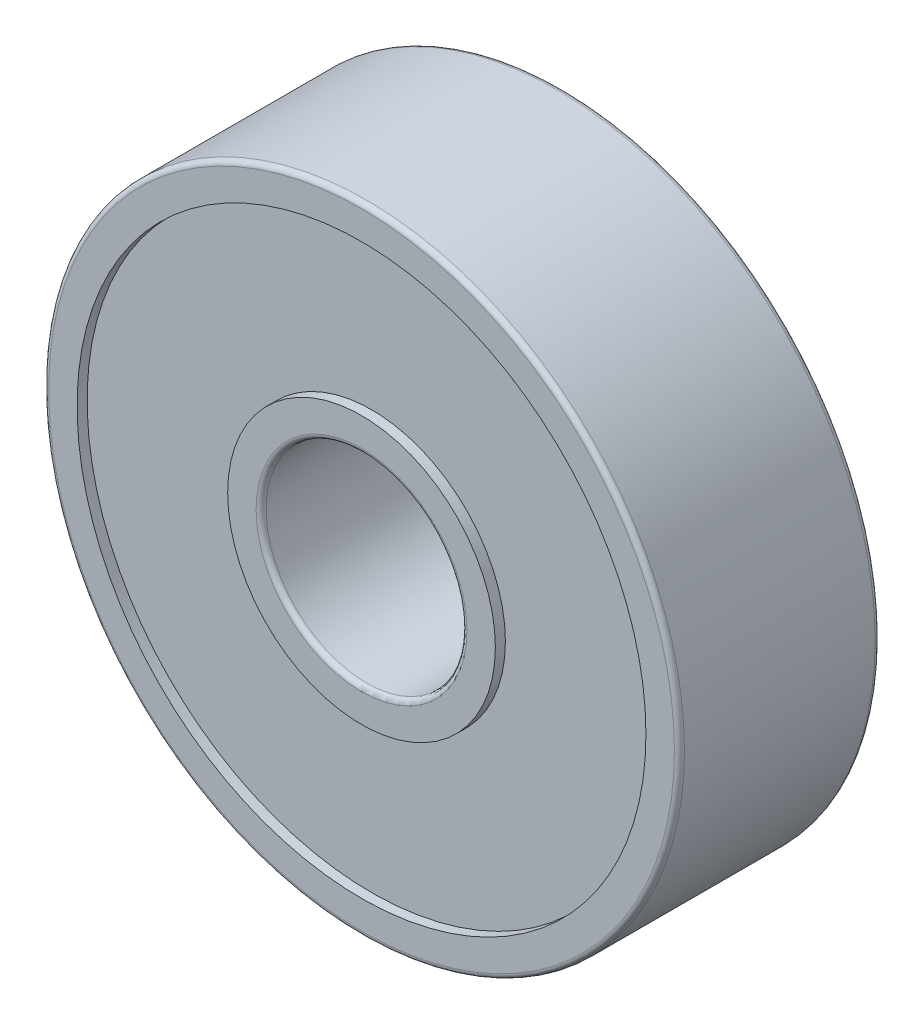
SolidWorks part; units mm, degrees
ref_plane "Front Plane" through (0, 0, 0) normal (0, 0, 1) x (1, 0, 0)
ref_plane "Top Plane" through (0, 0, 0) normal (0, 1, 0) x (1, 0, 0)
ref_plane "Right Plane" through (0, 0, 0) normal (1, 0, 0) x (0, 0, -1)
sketch "Sketch1" plane through (0, 0, 0) normal (0, 0, 1) x (1, 0, 0)
  circle A0 centre (0, 0) radius 3
  circle A1 centre (0, 0) radius 9.5
  dimension "D1" = 6
  dimension "D2" = 19
extrude "Boss-Extrude1" add sketch "Sketch1" along normal blind 6
sketch "Sketch2" plane through (0, 0, 6) normal (0, 0, 1) x (1, 0, 0)
  circle A0 centre (0, 0) radius 9.5 construction
  circle A2 centre (0, 0) radius 3 construction
  circle A3 centre (0, 0) radius 8.5
  circle A6 centre (0, 0) radius 4
  dimension "D1" = 1
  dimension "D2" = 1
extrude "Cut-Extrude1" cut sketch "Sketch2" against normal blind 0.3
extrude "Cut-Extrude2" cut sketch "Sketch2<2>" along normal blind 0.5 from surface starting at face at (9.5, 0, 0)
sketch "Sketch2<2>" plane through (0, 0, 6) normal (0, 0, 1) x (1, 0, 0) same geometry as "Sketch2"
fillet "Fillet1" radius 0.15 4 edges at (3, 0, 6) (9.5, 0, 6) (3, 0, 0) (9.5, 0, 0)
